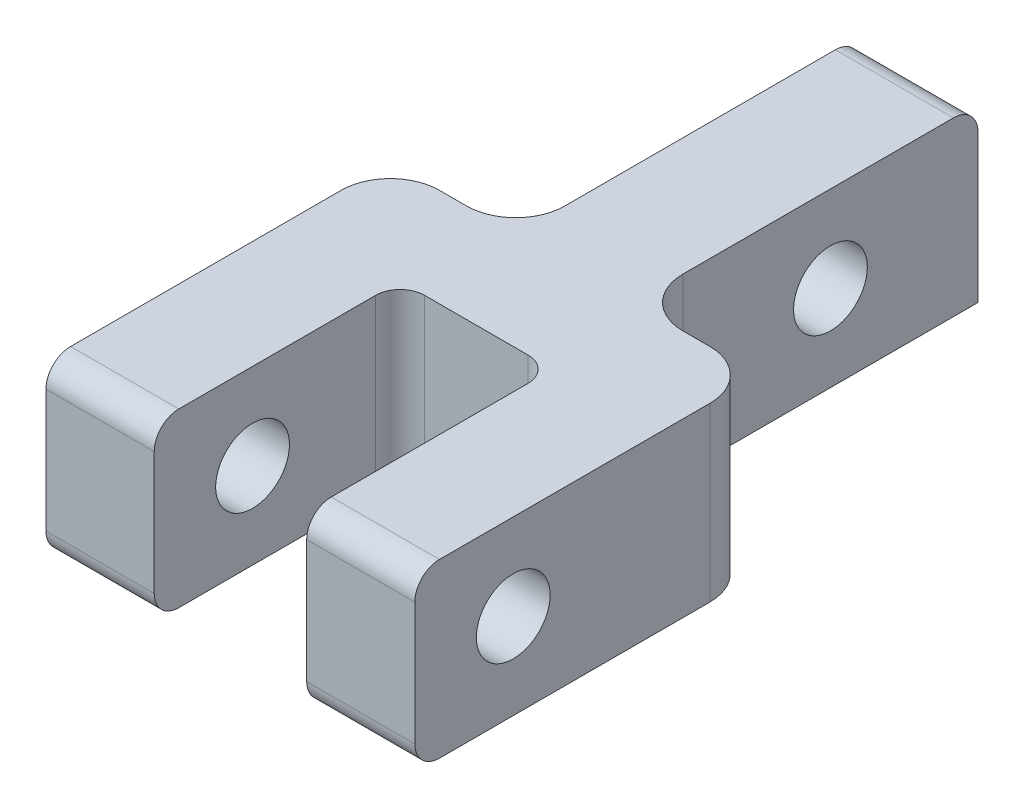
SolidWorks part; units mm, degrees
ref_plane "Alzado" through (0, 0, 0) normal (0, 0, 1) x (1, 0, 0)
ref_plane "Planta" through (0, 0, 0) normal (0, 1, 0) x (1, 0, 0)
ref_plane "Vista lateral" through (0, 0, 0) normal (1, 0, 0) x (0, 0, -1)
sketch "Croquis1" plane through (0, 0, 0) normal (1, 0, 0) x (0, 0, -1)
  line L0 (-13, 3.5) -> (13, 3.5)
  line L1 (14, -2.5) -> (14, -3.5)
  line L2 (-14, 0) -> (14, 0) construction
  line L3 (-14, 2.5) -> (-14, -2.5)
  line L4 (-13, -3.5) -> (13, -3.5)
  line L5 (14, 2.5) -> (14, -2.5)
  line L6 (14, -3.5) -> (13, -3.5)
  arc A0 (-14, -2.5) -> (-13, -3.5) centre (-13, -2.5) ccw
  arc A1 (-14, 2.5) -> (-13, 3.5) centre (-13, 2.5) cw
  arc A2 (13, -3.5) -> (14, -2.5) centre (13, -2.5) ccw construction
  arc A3 (13, 3.5) -> (14, 2.5) centre (13, 2.5) cw
  point P1 (0, 0)
  point P9 (-14, -3.5)
  point P13 (-14, 3.5)
  point P16 (14, -3.5)
  point P19 (14, 3.5)
  dimension "D3" = 1
  dimension "D4" = 1
  dimension "D1" = 3.5
  dimension "D2" = 28
extrude "Saliente-Extruir1" add sketch "Croquis1" along normal mid plane 4.8
sketch "Croquis2" plane through (0, 0, 0) normal (1, 0, 0) x (0, 0, -1)
  line L0 (-14, 2.5) -> (-14, -2.5) construction
  line L1 (14, -3.5) -> (14, 2.5) construction
  circle A0 centre (-10, 0) radius 1.5
  circle A1 centre (8, 0) radius 1.5
  dimension "D1" = 3
  dimension "D3" = 3
  dimension "D2" = 4
  dimension "D4" = 6
extrude "Cortar-Extruir1" cut sketch "Croquis2" against normal through all both and the other way through all
sketch "Croquis3" plane through (0, 0, 0) normal (1, 0, 0) x (0, 0, -1)
  line L0 (-14, 2.5) -> (-14, -2.5) construction
  line L1 (-14, 2.5) -> (-14, -2.5)
  line L2 (-13, 3.5) -> (0, 3.5)
  line L3 (13, 3.5) -> (-13, 3.5) construction
  line L4 (0, 3.5) -> (0, -3.5)
  line L5 (-13, -3.5) -> (14, -3.5) construction
  line L6 (0, -3.5) -> (-13, -3.5)
  circle A0 centre (-10, 0) radius 1.5 construction
  circle A1 centre (-10, 0) radius 1.5
  arc A2 (-13, 3.5) -> (-14, 2.5) centre (-13, 2.5) ccw construction
  arc A3 (-13, 3.5) -> (-14, 2.5) centre (-13, 2.5) ccw
  arc A4 (-14, -2.5) -> (-13, -3.5) centre (-13, -2.5) ccw construction
  arc A5 (-14, -2.5) -> (-13, -3.5) centre (-13, -2.5) ccw
extrude "Saliente-Extruir2" add sketch "Croquis3" along normal mid plane 15
sketch "Croquis4" plane through (0, 0, 0) normal (1, 0, 0) x (0, 0, -1)
  line L0 (-13, 3.5) -> (-4, 3.5)
  line L1 (0, 3.5) -> (-13, 3.5) construction
  line L2 (-4, 3.5) -> (-4, -3.5)
  line L3 (-13, -3.5) -> (0, -3.5) construction
  line L4 (-14, 2.5) -> (-14, -2.5)
  line L5 (-13, -3.5) -> (0, -3.5)
  line L6 (0, -3.5) -> (0, 3.5)
  line L7 (0, 3.5) -> (-13, 3.5)
  line L8 (-14, 2.5) -> (-14, -2.5)
  line L12 (-4, -3.5) -> (-13, -3.5)
  arc A2 (-13, 3.5) -> (-14, 2.5) centre (-13, 2.5) ccw
  arc A3 (-14, -2.5) -> (-13, -3.5) centre (-13, -2.5) ccw
  arc A4 (-13, 3.5) -> (-14, 2.5) centre (-13, 2.5) ccw
  arc A5 (-14, -2.5) -> (-13, -3.5) centre (-13, -2.5) ccw
  dimension "D2" = 10
  dimension "D1" = 0
extrude "Cortar-Extruir2" cut sketch "Croquis4" against normal mid plane 6.2
fillet "Redondeo1" radius 2 4 edges at (2.4, 0, 0) (-2.4, 0, 0) (7.5, 0, 0) (-7.5, 0, 0)
fillet "Redondeo2" radius 1 2 edges at (3.1, 0, 4) (-3.1, 0, 4)
